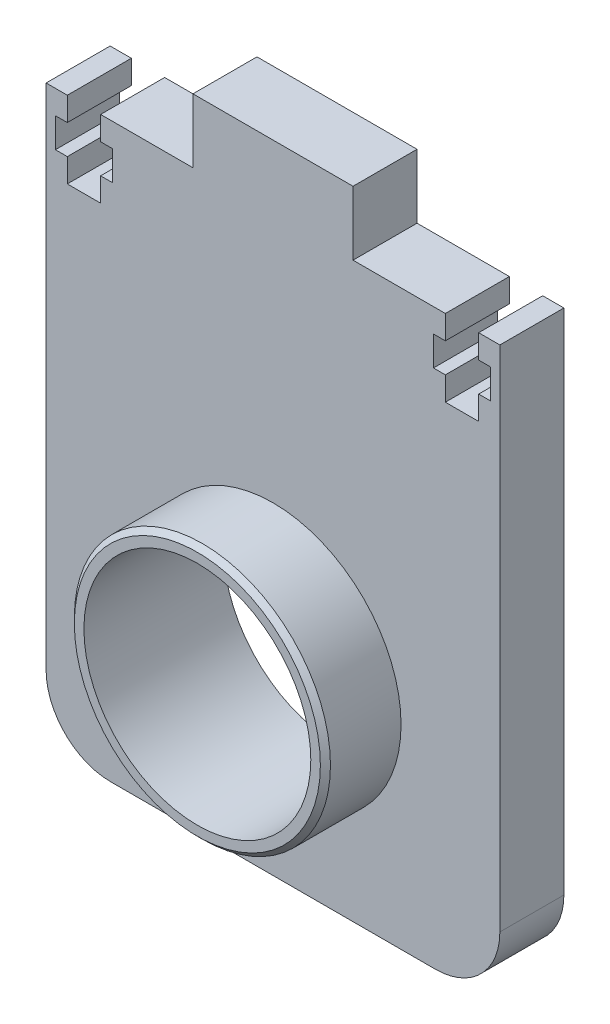
SolidWorks part; units mm, degrees
ref_plane "Front Plane" through (0, 0, 0) normal (0, 0, 1) x (1, 0, 0)
ref_plane "Top Plane" through (0, 0, 0) normal (0, 1, 0) x (1, 0, 0)
ref_plane "Right Plane" through (0, 0, 0) normal (1, 0, 0) x (0, 0, -1)
sketch "Sketch12" plane through (0, 0, 0) normal (0, 0, 1) x (1, 0, 0)
  line L0 (62.1258, 0) -> (62.1258, 126.33)
  line L1 (62.1258, 126.33) -> (152.1258, 126.33)
  line L2 (62.1258, 0) -> (152.1258, 0)
  line L3 (152.1258, 126.33) -> (152.1258, 0)
  line L4 (107.1258, 38.68) -> (107.1258, 126.33) construction
  circle A0 centre (107.1258, 38.68) radius 25.4
  circle A1 centre (107.1258, 38.68) radius 6.5
  dimension "D3" = 50.8
  dimension "D4" = 13
  dimension "D1" = 126.33
  dimension "D2" = 90
  dimension "D5" = 87.65
extrude "Boss-Extrude10" add sketch "Sketch12" along normal blind 12.7 separate body contours L1 L3 L2 L0
sketch "Sketch15" plane through (0, 0, 12.7) normal (0, 0, 1) x (1, 0, 0)
  line L0 (62.1258, 0) -> (152.1258, 0) construction
  circle A0 centre (107.1258, 38.6276) radius 25.4
  point P4 (107.1258, 0)
  dimension "D1" = 50.8
  dimension "D2" = 38.6276
extrude "Boss-Extrude11" add sketch "Sketch15" along normal blind 15
sketch "Sketch23" plane through (0, 0, 27.7) normal (0, 0, 1) x (1, 0, 0)
  circle A0 centre (107.1258, 38.6276) radius 22.5
  dimension "D1" = 45
extrude "Cut-Extrude7" cut sketch "Sketch23" against normal through all
fillet "Fillet2" radius 12.8 2 edges at (152.1258, 0, 6.35) (62.1258, 0, 6.35)
sketch "Sketch25" plane through (0, 0, 12.7) normal (0, 0, 1) x (1, 0, 0)
  line L0 (152.1258, 126.33) -> (152.1258, 113.63)
  line L1 (152.1258, 126.33) -> (152.1258, 12.8) construction
  line L2 (107.1258, 126.33) -> (107.1258, 98.7556)
  line L3 (62.1258, 12.8) -> (62.1258, 126.33) construction
  line L4 (62.1258, 113.63) -> (62.1258, 126.33)
  line L5 (123.0008, 113.63) -> (123.0008, 126.33)
  line L6 (62.1258, 126.33) -> (152.1258, 126.33) construction
  line L7 (123.0008, 126.33) -> (91.2508, 126.33)
  line L8 (91.2508, 126.33) -> (91.2508, 113.63)
  line L9 (91.2508, 113.63) -> (107.1258, 113.63)
  line L10 (107.1258, 113.63) -> (123.0008, 113.63)
  line L11 (152.1258, 113.63) -> (123.0008, 113.63)
  line L12 (123.0008, 126.33) -> (91.2508, 126.33)
  line L13 (91.2508, 113.63) -> (62.1258, 113.63)
  line M10 (152.1258, 12.8) -> (152.1258, 126.33)
  line M11 (152.1258, 126.33) -> (62.1258, 126.33)
  line M12 (62.1258, 126.33) -> (62.1258, 12.8)
  dimension "D1" = 12.7
  dimension "D2" = 31.75
extrude "Cut-Extrude9" cut sketch "Sketch25" against normal through all contours L13 L8 M11 M12 | L11 L5 M10 M11 region at (137.5633, 119.98, 12.7) region at (76.6883, 119.98, 12.7)
sketch "Sketch27" plane through (0, 0, 12.7) normal (0, 0, 1) x (1, 0, 0)
  line L0 (147.9178, 113.63) -> (147.9178, 108.931)
  line L1 (152.1258, 113.63) -> (123.0008, 113.63) construction
  line L2 (147.9178, 108.931) -> (150.2798, 108.931)
  line L3 (150.2798, 108.931) -> (150.2798, 103.089)
  line L4 (150.2798, 103.089) -> (147.9178, 103.089)
  line L5 (147.9178, 103.089) -> (147.9178, 98.39)
  line L6 (147.9178, 98.39) -> (141.3138, 98.39)
  line L7 (141.3138, 98.39) -> (141.3138, 103.089)
  line L8 (141.3138, 103.089) -> (138.9518, 103.089)
  line L9 (138.9518, 103.089) -> (138.9518, 108.931)
  line L10 (138.9518, 108.931) -> (141.3138, 108.931)
  line L11 (141.3138, 108.931) -> (141.3138, 113.63)
  line L12 (107.1258, 126.33) -> (107.1258, 67.6415) construction
  line L13 (91.2508, 126.33) -> (123.0008, 126.33) construction
  line L14 (72.9378, 103.089) -> (75.2998, 103.089)
  line L15 (75.2998, 103.089) -> (75.2998, 108.931)
  line L16 (75.2998, 108.931) -> (72.9378, 108.931)
  line L17 (72.9378, 108.931) -> (72.9378, 113.63)
  line L18 (66.3338, 113.63) -> (66.3338, 108.931)
  line L19 (66.3338, 108.931) -> (63.9718, 108.931)
  line L20 (63.9718, 108.931) -> (63.9718, 103.089)
  line L21 (63.9718, 103.089) -> (66.3338, 103.089)
  line L22 (66.3338, 103.089) -> (66.3338, 98.39)
  line L23 (66.3338, 98.39) -> (72.9378, 98.39)
  line L24 (72.9378, 98.39) -> (72.9378, 103.089)
  line L25 (147.9178, 113.63) -> (141.3138, 113.63)
  line L26 (72.9378, 113.63) -> (66.3338, 113.63)
  point P30 (144.6158, 113.63)
  point P31 (69.6358, 113.63)
  dimension "D1" = 6.604
  dimension "D2" = 11.328
  dimension "D3" = 15.24
  dimension "D4" = 5.842
  dimension "D5" = 74.98
ref_axis "Axis1" through (107.1258, 126.33, 12.7) along (0, -1, 0)
extrude "Cut-Extrude10" cut sketch "Sketch27" against normal through all
chamfer "Chamfer1" distance 1 angle 45 1 edges at (132.5258, 38.6276, 27.7)
